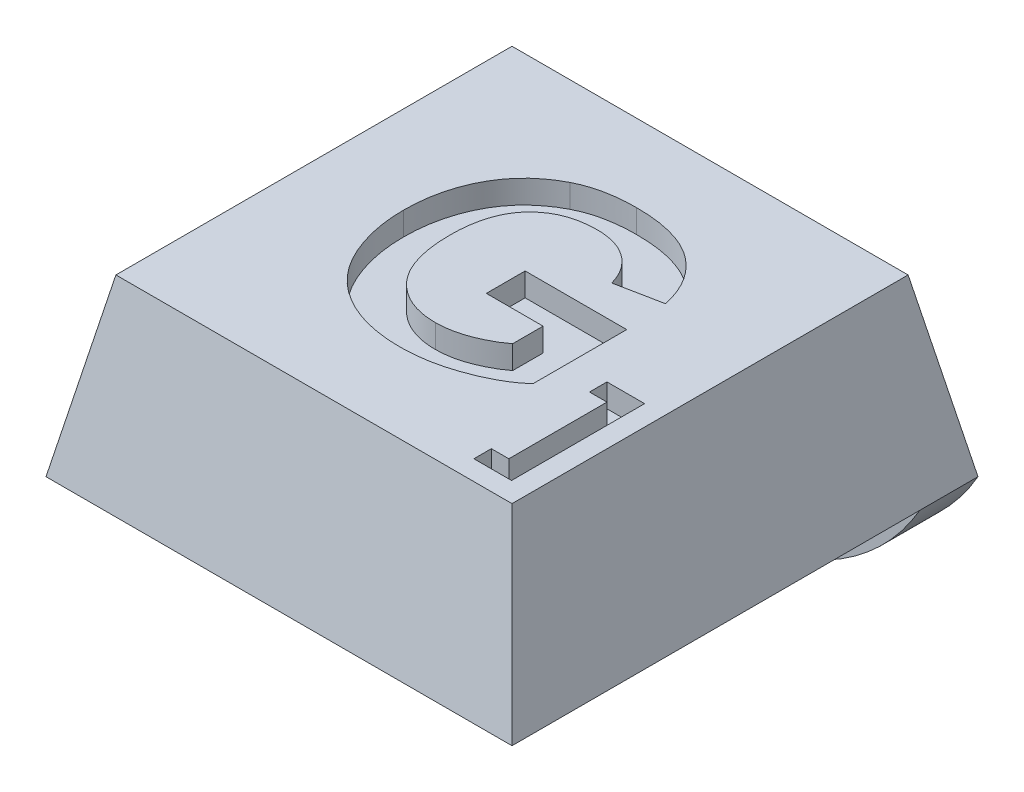
SolidWorks part; units mm, degrees
ref_plane "Front Plane" through (0, 0, 0) normal (0, 0, 1) x (1, 0, 0)
ref_plane "Top Plane" through (0, 0, 0) normal (0, 1, 0) x (1, 0, 0)
ref_plane "Right Plane" through (0, 0, 0) normal (1, 0, 0) x (0, 0, -1)
sketch "Sketch1" plane through (0, 0, 0) normal (0, 1, 0) x (1, 0, 0)
  line L1 (0, 0) -> (8, 0)
  line L2 (0, 0) -> (0, 8)
  line L3 (0, 8) -> (8, 8)
  line L4 (8, 0) -> (8, 8)
  dimension "D1" = 8
  dimension "D2" = 8
extrude "Boss-Extrude1" add sketch "Sketch1" along normal blind 3
sketch "Sketch2" plane through (0, 0, 0) normal (0, 0, 1) x (1, 0, 0)
  line L0 (0, 0) -> (0.6, 3)
  line L1 (0, 3) -> (8, 3) construction
  line L2 (0.6, 3) -> (0, 3)
  line L3 (0, 3) -> (0, 0)
  line L4 (8, 0) -> (7.4, 3)
  line L5 (7.4, 3) -> (8, 3)
  line L6 (8, 3) -> (8, 0)
  dimension "D1" = 0.6
  dimension "D2" = 0.6
extrude "Cut-Extrude1" cut sketch "Sketch2" against normal through all both and the other way through all
sketch "Sketch3" plane through (0, 0, 0) normal (1, 0, 0) x (0, 0, -1)
  line L0 (0, 0) -> (0.6, 3)
  line L1 (8, 3) -> (0, 3) construction
  line L2 (0.6, 3) -> (0, 3)
  line L3 (0, 3) -> (0, 0)
  line L4 (8, 3) -> (7.4, 3)
  line L5 (7.4, 3) -> (8, 0)
  line L6 (8, 3) -> (8, 0)
  dimension "D1" = 0.6
  dimension "D2" = 0.6
extrude "Cut-Extrude2" cut sketch "Sketch3" along normal blind 11
sketch "Sketch4" plane through (0, 0, 0) normal (0, -1, 0) x (1, 0, 0)
  line L0 (8, 0) -> (8, -8) construction
  line L3 (0, 0) -> (8, 0) construction
  circle A0 centre (4, -3.75) radius 1.8
  dimension "D1" = 3.6
  dimension "D2" = 4
  dimension "D3" = 3.75
extrude "Cut-Extrude3" cut sketch "Sketch4" against normal blind 0.8
sketch "Sketch5" plane through (0, 0, 0) normal (0, -1, 0) x (1, 0, 0)
  line L0 (8, 0) -> (8, -8) construction
  line L1 (0, -8) -> (8, -8)
  line L2 (0, -8) -> (0, -7)
  line L3 (0, -7) -> (8, -7)
  line L4 (8, -8) -> (8, -7)
  dimension "D1" = 1
extrude "Boss-Extrude2" add sketch "Sketch5" along normal blind 2
fillet "Fillet1" radius 4 2 edges at (8, -2, -7.5) (0, -2, -7.5)
sketch "Sketch6" plane through (0, 3, 0) normal (0, 1, 0) x (1, 0, 0)
  text T0 "G" font "Arial" height 4
extrude "Cut-Extrude4" cut sketch "Sketch6" against normal blind 0.4
sketch "Sketch7" plane through (0, 3, 0) normal (0, 1, 0) x (1, 0, 0)
  text T0 "]" font "Arial" height 1.8
extrude "Cut-Extrude5" cut sketch "Sketch7" against normal blind 0.4
